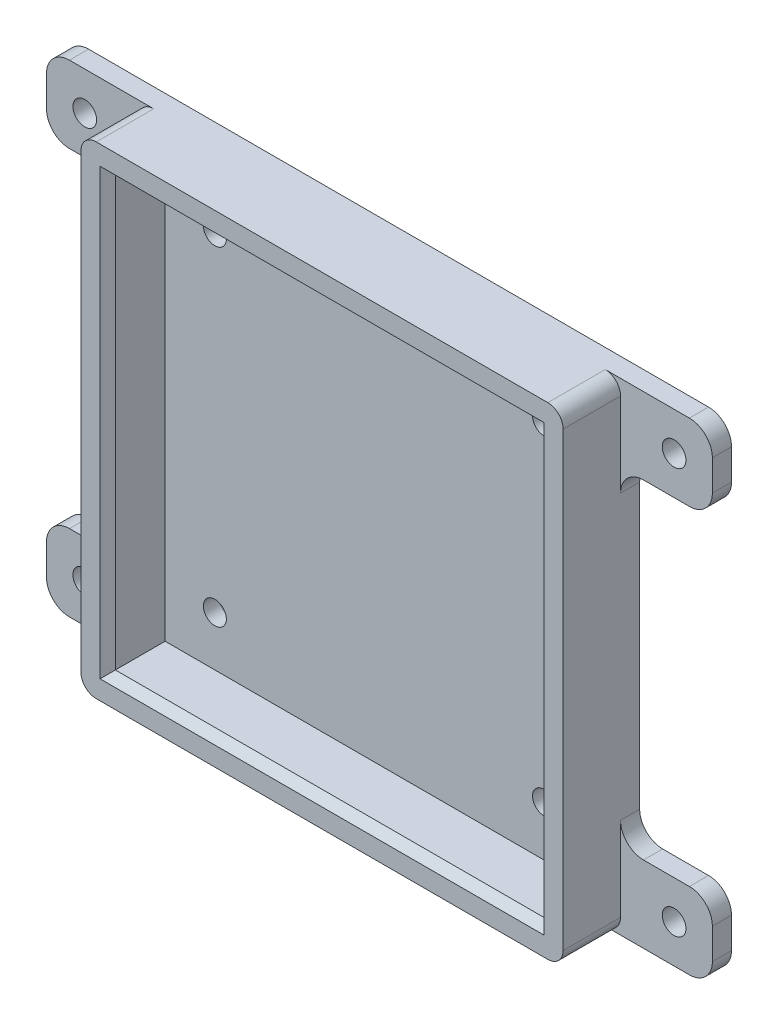
SolidWorks part; units mm, degrees
note: The reader was unsure of these and kept them because the rebuilt part matched: shared geometry of "Sketch1<3>", "Sketch1<4>".
material "ABS"
ref_plane "Front Plane" through (0, 0, 0) normal (0, 0, 1) x (1, 0, 0)
ref_plane "Top Plane" through (0, 0, 0) normal (0, 1, 0) x (1, 0, 0)
ref_plane "Right Plane" through (0, 0, 0) normal (1, 0, 0) x (0, 0, -1)
sketch "Sketch1" plane through (0, 0, 0) normal (0, 0, 1) x (1, 0, 0)
  line L0 (-31.5, -71.5) -> (-31.5, -8.5)
  line L1 (-28, -68) -> (28, -68)
  line L2 (-28, -68) -> (-28, -12)
  line L3 (-28, -12) -> (28, -12)
  line L4 (28, -68) -> (28, -12)
  line L5 (-28, -68) -> (28, -12) construction
  line L6 (-28, -12) -> (28, -68) construction
  line L7 (-31.5, -8.5) -> (31.5, -8.5)
  line L8 (31.5, -71.5) -> (31.5, -8.5)
  line L9 (-31.5, -71.5) -> (31.5, -71.5)
  line L10 (0, -40) -> (50000, -40) construction
  line L11 (-43.5, -71.5) -> (43.5, -71.5)
  line L12 (-43.5, -71.5) -> (-43.5, -61.5)
  line L13 (-43.5, -8.5) -> (43.5, -8.5)
  line L14 (43.5, -71.5) -> (43.5, -61.5)
  line L15 (-43.5, -71.5) -> (43.5, -8.5) construction
  line L16 (-43.5, -8.5) -> (43.5, -71.5) construction
  line L17 (0, 0) -> (0, 50000) construction
  line L18 (-43.5, -18.5) -> (-31.5, -18.5)
  line L19 (-43.5, -61.5) -> (-31.5, -61.5)
  line L20 (43.5, -61.5) -> (31.5, -61.5)
  line L21 (43.5, -18.5) -> (31.5, -18.5)
  line L22 (-43.5, -18.5) -> (-43.5, -8.5)
  line L23 (43.5, -18.5) -> (43.5, -8.5)
  circle A1 centre (-38.5, -13.5) radius 1.55
  circle A2 centre (-38.5, -66.5) radius 1.55
  circle A3 centre (38.5, -66.5) radius 1.55
  circle A4 centre (38.5, -13.5) radius 1.55
  point P10 (0, -40)
  dimension "D5" = 3.1
  dimension "D1" = 56
  dimension "D2" = 56
  dimension "D4" = 40
  dimension "D6" = 5
  dimension "D7" = 5
  dimension "D8" = 7
  dimension "D9" = 5
  dimension "D3" = 3.5
extrude "Boss-Extrude1" add sketch "Sketch1" along normal blind 2.5 contours L1 L4 L3 L2 | L0 L9 L8 L7 L4 L1 L2 L3 | L21 L23 L13 L8 A4 | L14 L20 L8 L11 A3 | L19 L12 L11 L0 A2 | L22 L18 L0 L13 A1
extrude "Boss-Extrude2" add sketch "Sketch1<3>" along normal blind 10 contours L0 L9 L8 L7 L4 L1 L2 L3
sketch "Sketch1<3>" plane through (0, 0, 0) normal (0, 0, 1) x (1, 0, 0) same geometry as "Sketch1"
extrude "Boss-Extrude3" add sketch "Sketch1<4>" along normal blind 2 contours L19 L12 L11 L0 A2 | L22 L18 L0 L13 A1 | L21 L23 L13 L8 A4 | L14 L20 L8 L11 A3
sketch "Sketch1<4>" plane through (0, 0, 0) normal (0, 0, 1) x (1, 0, 0) same geometry as "Sketch1"
fillet "Fillet1" radius 3 12 edges at (43.5, -18.5, 1.25) (43.5, -8.5, 1.25) (-31.5, -18.5, 1.25) (-31.5, -61.5, 1.25) (-43.5, -61.5, 1.25) (-43.5, -71.5, 1.25) (43.5, -71.5, 1.25) (43.5, -61.5, 1.25) (31.5, -61.5, 1.25) (31.5, -18.5, 1.25) (-43.5, -18.5, 1.25) (-43.5, -8.5, 1.25)
fillet "Fillet2" radius 2 4 edges at (31.5, -71.5, 6.25) (31.5, -8.5, 6.25) (-31.5, -71.5, 6.25) (-31.5, -8.5, 6.25)
chamfer "Chamfer1" distance 1 4 edges at (0, -12, 10) (28, -40, 10) (0, -68, 10) (-28, -40, 10)
sketch "Sketch2" plane through (0, 0, 0) normal (0, 0, -1) x (-1, 0, 0)
  line L0 (0, -40) -> (50000, -40) construction
  line L1 (-21.5, -61.5) -> (21.5, -61.5)
  line L2 (-21.5, -61.5) -> (-21.5, -18.5)
  line L3 (-21.5, -18.5) -> (21.5, -18.5)
  line L4 (21.5, -61.5) -> (21.5, -18.5)
  line L5 (-21.5, -61.5) -> (21.5, -18.5) construction
  line L6 (-21.5, -18.5) -> (21.5, -61.5) construction
  line L7 (0, -30) -> (0, 49970) construction
  line L8 (40.5, -8.5) -> (-40.5, -8.5) construction
  line L9 (40.5, -71.5) -> (-40.5, -71.5) construction
  circle A0 centre (-21.5, -18.5) radius 1.5
  circle A1 centre (-21.5, -61.5) radius 1.5
  circle A2 centre (21.5, -61.5) radius 1.5
  circle A3 centre (21.5, -18.5) radius 1.5
  point P0 (0, -40)
  dimension "D2" = 3
  dimension "D1" = 43
extrude "Cut-Extrude1" cut sketch "Sketch2" against normal through all both and the other way through all contours A1 | A2 | A3 | A0
fillet "Fillet3" radius 0.5 4 edges
